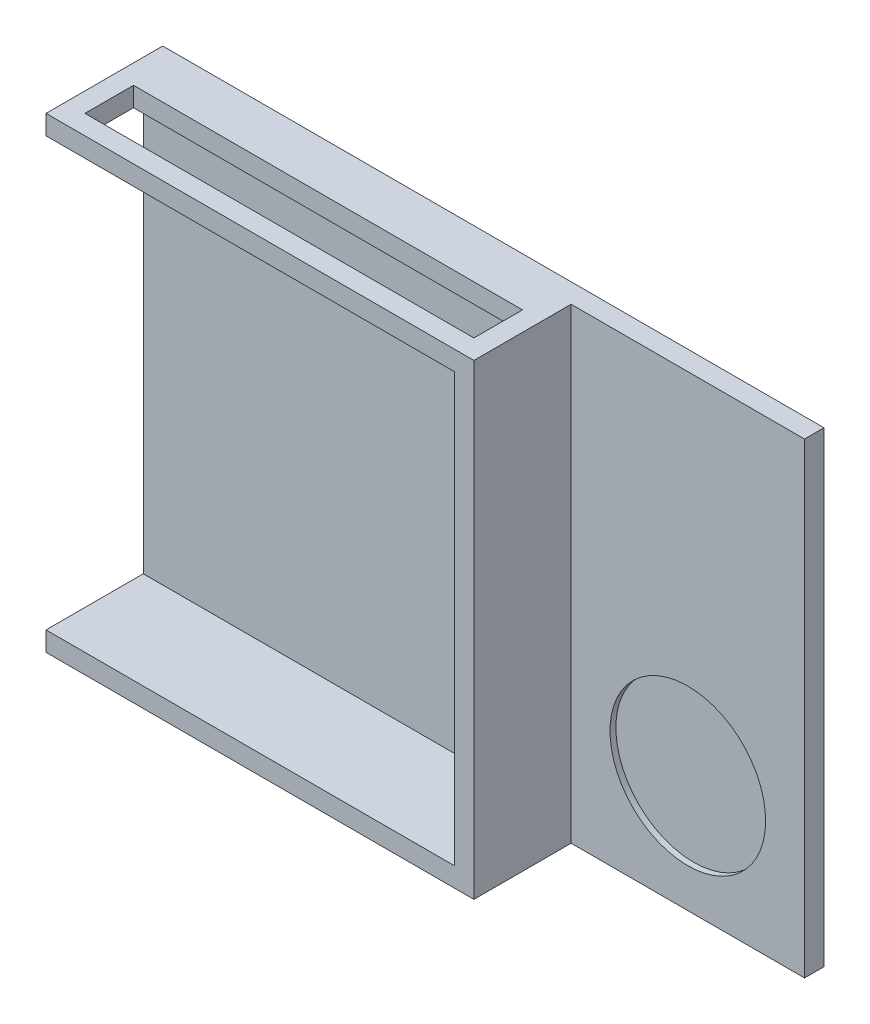
SolidWorks part; units mm, degrees
ref_plane "Plano frontal" through (0, 0, 0) normal (0, 0, 1) x (1, 0, 0)
ref_plane "Plano superior" through (0, 0, 0) normal (0, 1, 0) x (1, 0, 0)
ref_plane "Plano direito" through (0, 0, 0) normal (1, 0, 0) x (0, 0, -1)
sketch "Esboço1" plane through (0, 0, 0) normal (0, 0, 1) x (1, 0, 0)
  line L3 (-99.2177, 25.0239) -> (70.7823, 25.0239)
  line L4 (70.7823, 0) -> (70.7823, 25.0239)
  line L7 (-99.2177, 25.0239) -> (-269.2177, 25.0239)
  line L8 (-269.2177, 0) -> (-269.2177, 25.0239)
  line L11 (-99.2177, -214.9761) -> (-269.2177, -214.9761)
  line L12 (-269.2177, 0) -> (-269.2177, -214.9761)
  line L15 (-99.2177, -214.9761) -> (70.7823, -214.9761)
  line L16 (70.7823, 0) -> (70.7823, -214.9761)
  dimension "D1" = 340
  dimension "D2" = 240
extrude "Ressalto-extrusão1" add sketch "Esboço1" along normal blind 10 contours L7 L8 L12 L11 L15 L16 L4 L3
sketch "Esboço2" plane through (0, 0, 10) normal (0, 0, 1) x (1, 0, 0)
  line L8 (-49.2177, -214.9761) -> (-269.2177, -214.9761)
  line L9 (-49.2177, -214.9761) -> (-49.2177, -204.9761)
  line L10 (-49.2177, -204.9761) -> (-269.2177, -204.9761)
  line L11 (-269.2177, -214.9761) -> (-269.2177, -204.9761)
  line L12 (-269.2177, 25.0239) -> (-269.2177, -214.9761) construction
  line L13 (-269.2177, -214.9761) -> (70.7823, -214.9761) construction
  line L14 (-269.2177, 25.0239) -> (70.7823, 25.0239) construction
  line L15 (-49.2177, 25.0239) -> (-269.2177, 25.0239)
  line L16 (-49.2177, 25.0239) -> (-49.2177, 15.0239)
  line L17 (-49.2177, 15.0239) -> (-269.2177, 15.0239)
  line L18 (-269.2177, 25.0239) -> (-269.2177, 15.0239)
  line L20 (-49.2177, 15.0239) -> (-59.2177, 15.0239)
  line L21 (-49.2177, 15.0239) -> (-49.2177, -214.9761)
  line L22 (-49.2177, -214.9761) -> (-59.2177, -214.9761)
  line L23 (-59.2177, 15.0239) -> (-59.2177, -214.9761)
  dimension "D3" = 220
  dimension "D4" = 10
  dimension "D5" = 10
  dimension "D6" = 10
extrude "Ressalto-extrusão4" add sketch "Esboço2" along normal blind 50 contours L8 L11 L10 L9 | L16 L15 L18 L17 | L20 L23 L22 L21
sketch "Esboço7" plane through (0, 0, 10) normal (0, 0, 1) x (1, 0, 0)
  line L0 (70.7823, -214.9761) -> (70.7823, 25.0239) construction
  line L1 (10.7823, -214.9761) -> (10.7823, -154.9761)
  line L3 (-49.2177, -214.9761) -> (-49.2177, 25.0239) construction
  line L4 (-49.2177, -214.9761) -> (70.7823, -214.9761) construction
  line L5 (70.7823, -84.9761) -> (-49.2177, -84.9761)
  line L7 (70.7823, -84.9761) -> (70.7823, -74.9761)
  line L8 (70.7823, -74.9761) -> (-49.2177, -74.9761)
  line L9 (-49.2177, -84.9761) -> (-49.2177, -74.9761)
  circle A0 centre (10.7823, -154.9761) radius 40
  dimension "D2" = 80
  dimension "D1" = 60
  dimension "D3" = 60
  dimension "D4" = 70
  dimension "D5" = 10
extrude "Corte-extrusão1" cut sketch "Esboço7" against normal blind 3 contours A0
sketch "Esboço21" plane through (0, 25.0239, 0) normal (0, 1, 0) x (1, 0, 0)
  line L0 (-269.2177, -60) -> (-269.2177, 0) construction
  line L1 (-259.2177, -25) -> (-59.2177, -25)
  line L2 (-259.2177, -25) -> (-259.2177, -50)
  line L3 (-259.2177, -50) -> (-59.2177, -50)
  line L4 (-59.2177, -25) -> (-59.2177, -50)
  line L5 (-49.2177, -60) -> (-269.2177, -60) construction
  line L6 (70.7823, 0) -> (-269.2177, 0) construction
  dimension "D1" = 10
  dimension "D2" = 10
  dimension "D3" = 25
  dimension "D4" = 200
extrude "Corte-extrusão5" cut sketch "Esboço21" against normal blind 100 contours L1 L4 L3 L2
sketch "Esboço23" plane through (0, 15.0239, 0) normal (0, -1, 0) x (1, 0, 0)
  line L0 (-59.2177, 60) -> (-269.2177, 60) construction
  line L1 (-269.2177, 57.5) -> (-119.2177, 57.5)
  line L2 (-269.2177, 57.5) -> (-269.2177, 52.5)
  line L3 (-269.2177, 52.5) -> (-119.2177, 52.5)
  line L4 (-119.2177, 57.5) -> (-119.2177, 52.5)
  line L7 (-269.2177, 60) -> (-269.2177, 10) construction
  dimension "D1" = 5
  dimension "D2" = 2.5
  dimension "D3" = 150
  dimension "D4" = 0
extrude "Corte-extrusão6" cut sketch "Esboço23" against normal blind 1.25 and the other way blind 161.25 contours L1 L4 L3 L2
sketch "Esboço27" plane through (0, 0, 10) normal (0, 0, 1) x (1, 0, 0)
sketch "Esboço28" plane through (0, 0, 10) normal (0, 0, 1) x (1, 0, 0)
  line L0 (-49.2177, -214.9761) -> (-49.2177, 25.0239) construction
  line L1 (70.7823, -74.9761) -> (-49.2177, -74.9761)
  line L2 (70.7823, -74.9761) -> (70.7823, -84.9761)
  line L3 (70.7823, -84.9761) -> (-49.2177, -84.9761)
  line L4 (-49.2177, -74.9761) -> (-49.2177, -84.9761)
  line L5 (70.7823, -214.9761) -> (70.7823, 25.0239) construction
  line L6 (-49.2177, 25.0239) -> (70.7823, 25.0239) construction
  line L7 (70.7823, -74.9761) -> (50.4319, -74.9761)
  line L8 (70.7823, -74.9761) -> (70.7823, 25.0239)
  line L9 (70.7823, 25.0239) -> (50.4319, 25.0239)
  line L10 (50.4319, -74.9761) -> (50.4319, 25.0239)
  line L11 (-59.2177, 15.0239) -> (-269.2177, 15.0239) construction
  line L12 (-49.2177, -74.9761) -> (-42.1528, -74.9761)
  line L13 (-49.2177, -74.9761) -> (-49.2177, 25.0239)
  line L14 (-49.2177, 25.0239) -> (-42.1528, 25.0239)
  line L15 (-42.1528, -74.9761) -> (-42.1528, 25.0239)
  line L16 (-42.1528, 25.0239) -> (50.4319, 25.0239)
  line L17 (-42.1528, 25.0239) -> (-42.1528, 11.0031)
  line L18 (-42.1528, 11.0031) -> (50.4319, 11.0031)
  line L19 (50.4319, 25.0239) -> (50.4319, 11.0031)
  circle A0 centre (10.7823, -154.9761) radius 40 construction
  dimension "D1" = 10
  dimension "D2" = 70
